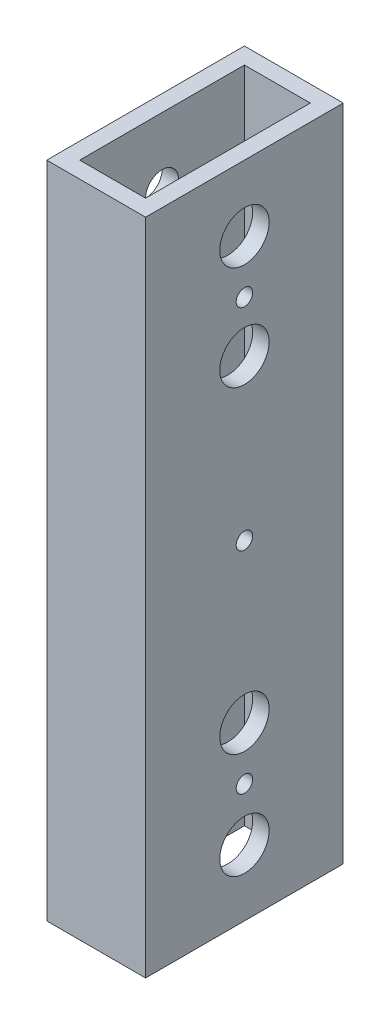
SolidWorks part; units mm, degrees
ref_plane "Front" through (0, 0, 0) normal (0, 0, 1) x (1, 0, 0)
ref_plane "Top" through (0, 0, 0) normal (0, 1, 0) x (1, 0, 0)
ref_plane "Right" through (0, 0, 0) normal (1, 0, 0) x (0, 0, -1)
sketch "Sketch1" plane through (0, 0, 0) normal (0, 1, 0) x (1, 0, 0)
  line L0 (3.175, 3.175) -> (15.875, 3.175)
  line L1 (0, 0) -> (19.05, 0)
  line L2 (0, 0) -> (0, 38.1)
  line L3 (0, 38.1) -> (19.05, 38.1)
  line L4 (19.05, 0) -> (19.05, 38.1)
  line L5 (15.875, 3.175) -> (15.875, 34.925)
  line L6 (3.175, 34.925) -> (15.875, 34.925)
  line L7 (3.175, 3.175) -> (3.175, 34.925)
  dimension "D1" = 38.1
  dimension "D2" = 19.05
  dimension "D3" = 3.175
extrude "Boss-Extrude1" add sketch "Sketch1" along normal blind 127
sketch "Sketch2" plane through (19.05, 0, 0) normal (1, 0, 0) x (0, 0, -1)
  line L0 (19.05, 0) -> (19.05, 12.7) construction
  line L1 (0, 0) -> (38.1, 0) construction
  line L2 (19.05, 12.7) -> (19.05, 32.7) construction
  line L3 (0, 63.5) -> (38.1, 63.5) construction
  line L4 (0, 127) -> (0, 0) construction
  line L5 (38.1, 127) -> (38.1, 0) construction
  line L6 (19.05, 114.3) -> (19.05, 94.3) construction
  circle A0 centre (19.05, 12.7) radius 3.175
  circle A1 centre (19.05, 32.7) radius 3.175
  circle A2 centre (19.05, 94.3) radius 3.175
  circle A3 centre (19.05, 114.3) radius 3.175
  dimension "D2" = 6.35
  dimension "D1" = 12.7
  dimension "D3" = 20
extrude "Cut-Extrude1" cut sketch "Sketch2" against normal through all
sketch "Sketch3" plane through (19.05, 0, 0) normal (1, 0, 0) x (0, 0, -1)
  circle A0 centre (19.05, 114.3) radius 4.7625
  circle A1 centre (19.05, 94.3) radius 4.7625
  circle A2 centre (19.05, 33.0594) radius 4.7625
  circle A4 centre (19.05, 12.7) radius 4.7625
  dimension "D1" = 9.525
extrude "Cut-Extrude2" cut sketch "Sketch3" against normal up to next
sketch "Sketch4" plane through (19.05, 0, 0) normal (1, 0, 0) x (0, 0, -1)
  line L0 (19.05, 28.2969) -> (19.05, 17.4625) construction
  line L1 (0, 63.5) -> (38.1, 63.5) construction
  line L2 (0, 127) -> (0, 0) construction
  line L3 (38.1, 127) -> (38.1, 0) construction
  circle A0 centre (19.05, 33.0594) radius 4.7625 construction
  circle A1 centre (19.05, 12.7) radius 4.7625 construction
  circle A2 centre (19.05, 22.8797) radius 1.5875
  circle A3 centre (19.05, 63.5) radius 1.5875
  circle A4 centre (19.05, 104.1203) radius 1.5875
  dimension "D1" = 3.175
  dimension "D2" = 40.6203
extrude "UChan_Mount" cut sketch "Sketch4" against normal through all
sketch "Sketch5" plane through (0, 0, 0) normal (-1, 0, 0) x (0, 0, 1)
  circle A0 centre (-19.05, 104.1203) radius 4.7625
  circle A1 centre (-19.05, 63.5) radius 4.7625
  circle A2 centre (-19.05, 22.8797) radius 4.7625
  dimension "D1" = 9.525
extrude "Cut-Extrude4" cut sketch "Sketch5" against normal up to next
ref_plane "Mid_Plane" through (0, 0, -19.05) normal (0, 0, -1) x (-1, 0, 0)
